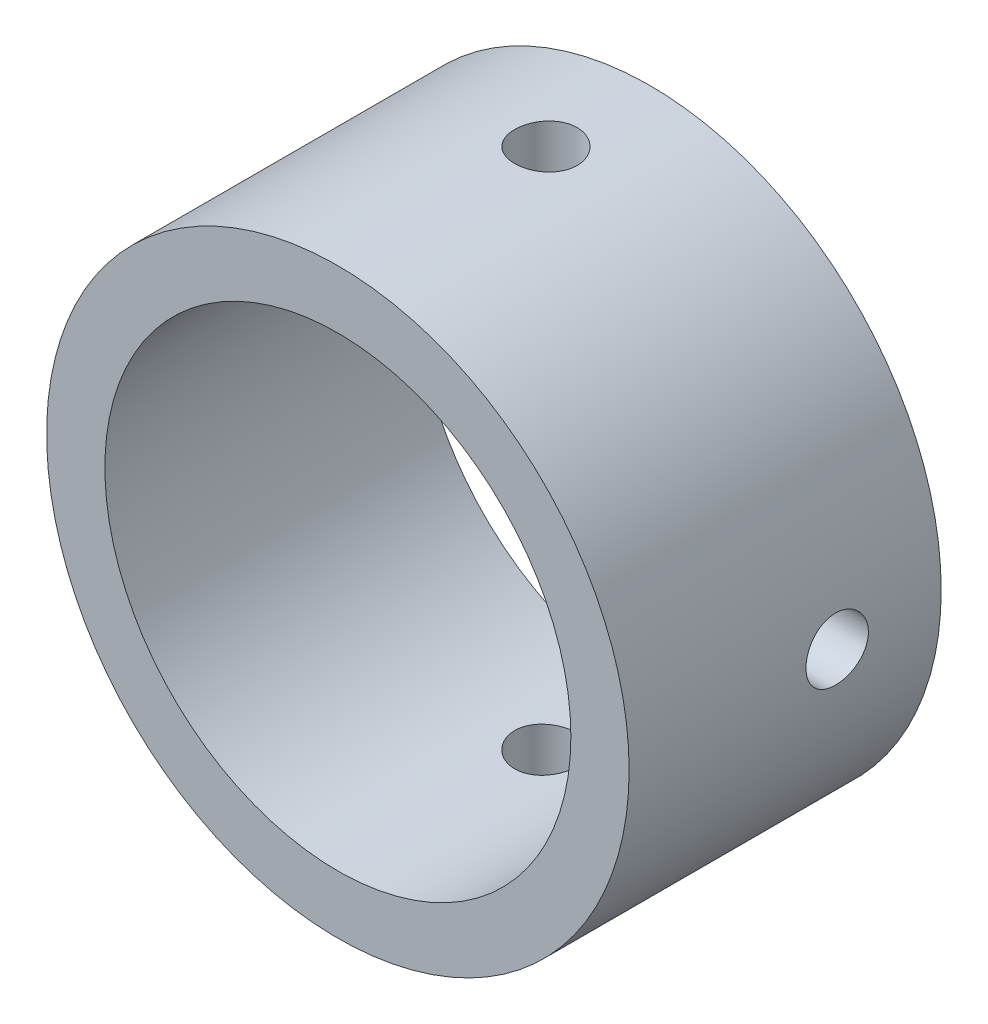
SolidWorks part; units mm, degrees
ref_plane "Front Plane" through (0, 0, 0) normal (0, 0, 1) x (1, 0, 0)
ref_plane "Top Plane" through (0, 0, 0) normal (0, 1, 0) x (1, 0, 0)
ref_plane "Right Plane" through (0, 0, 0) normal (1, 0, 0) x (0, 0, -1)
ref_axis "Z" through (0, 0, 5.75) along (0, 0, -1)
ref_axis "X" through (17.0818, 0, 0) along (-1, 0, 0)
ref_axis "Y" through (0, 15.4, 0) along (0, -1, 0)
sketch "Sketch1" plane through (0, 0, 0) normal (0, 0, 1) x (1, 0, 0)
  circle A0 centre (0, 0) radius 14
  circle A1 centre (0, 0) radius 11.2
  dimension "D1" = 28
  dimension "D2" = 22.4
extrude "Boss-Extrude1" add sketch "Sketch1" against normal blind 5 and the other way blind 10
sketch "Sketch2" plane through (0, 0, 0) normal (0, 1, 0) x (1, 0, 0)
  line L0 (-15.4, 0) -> (15.4, 0) construction
  line L1 (0, -8.25) -> (0, 8.25) construction
  circle A0 centre (0, 0) radius 1.5
  dimension "D1" = 3
extrude "Cut-Extrude1" cut sketch "Sketch2" against normal through all both and the other way through all
sketch "Sketch3" plane through (0, 0, 0) normal (1, 0, 0) x (0, 0, -1)
  circle A0 centre (0, 0) radius 1.5
  dimension "D1" = 3
extrude "Cut-Extrude2" cut sketch "Sketch3" along normal through all
equation "\"EyeDiameter\" = 28"
equation "\"BasePlaneDistance\" = 45"
equation "\"EyeClearance\" = 2"
equation "\"EyeOD\"= \"EyeDiameter\""
equation "\"D1@Sketch1\"=\"EyeOD\""
equation "\"D2@Sketch1\"=\"EyeDiameter\"*0.8"
equation "\"pinHoleDiameter\"= 3"
equation "\"D1@Sketch2\"=\"pinHoleDiameter\""
equation "\"D1@Sketch3\"=\"pinHoleDiameter\""
